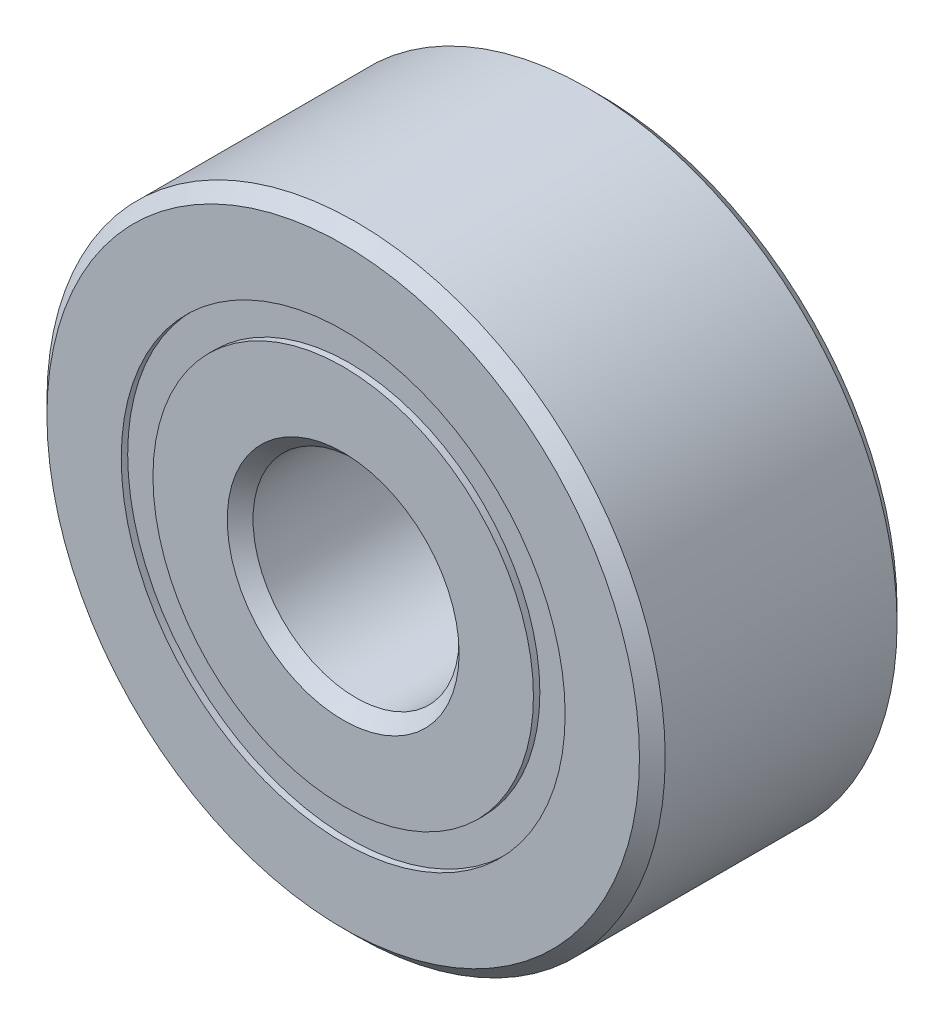
SolidWorks part; units mm, degrees
ref_plane "Front Plane" through (0, 0, 0) normal (0, 0, 1) x (1, 0, 0)
ref_plane "Top Plane" through (0, 0, 0) normal (0, 1, 0) x (1, 0, 0)
ref_plane "Right Plane" through (0, 0, 0) normal (1, 0, 0) x (0, 0, -1)
sketch "Sketch1" plane through (0, 0, 0) normal (1, 0, 0) x (0, 0, -1)
  line L0 (-1.9844, 0) -> (1.9844, 0) construction
  line L1 (0, 4.7625) -> (0, -4.7625) construction
  line L2 (1.7859, 4.7625) -> (-1.7859, 4.7625)
  line L3 (-1.7859, 4.7625) -> (-1.9844, 4.5641)
  line L4 (-1.9844, 4.5641) -> (-1.9844, 3.4192)
  line L5 (-1.9844, 3.4192) -> (-0.8819, 3.4192)
  line L6 (1.9844, 3.4192) -> (0.8819, 3.4192)
  line L7 (1.9844, 4.5641) -> (1.9844, 3.4192)
  line L8 (1.7859, 4.7625) -> (1.9844, 4.5641)
  line L9 (0, 4.7625) -> (0, 3.175) construction
  line L10 (0, 3.175) -> (0, 1.5875) construction
  arc A0 (-0.8819, 3.4192) -> (0.8819, 3.4192) centre (0, 3.175) cw
  point P14 (0, 1.5875)
  dimension "Width" = 3.9688
  dimension "OD" = 9.525
  dimension "D1" = 45
  dimension "D2" = 0.1984
  dimension "Shaft Dia" = 3.175
  dimension "D3" = 1.7639
  dimension "D4" = 0.2442
revolve "Revolve1" add sketch "Sketch1" angle 360 about L0
sketch "Sketch3" plane through (0, 0, 0) normal (1, 0, 0) x (0, 0, -1)
  line L0 (-1.9844, 2.9308) -> (-0.8819, 2.9308)
  line L1 (0, 4.7625) -> (0, -4.7625) construction
  line L2 (-1.9844, 4.5641) -> (-1.9844, 3.4192) construction
  line L3 (-1.9844, 2.9308) -> (-1.9844, 1.7859)
  line L4 (-1.7859, 4.7625) -> (-1.9844, 4.5641) construction
  line L5 (-1.9844, 1.7859) -> (-1.7859, 1.5875)
  line L6 (-1.7859, 1.5875) -> (1.7859, 1.5875)
  line L7 (1.7859, 4.7625) -> (1.7859, -4.7625) construction
  line L8 (1.7859, 1.5875) -> (1.9844, 1.7859)
  line L9 (1.9844, -4.5641) -> (1.9844, 4.5641) construction
  line L10 (1.9844, 1.7859) -> (1.9844, 2.9308)
  line L11 (1.9844, 2.9308) -> (0.8819, 2.9308)
  line L13 (1.7859, 4.7625) -> (1.9844, 4.5641) construction
  arc A0 (0.8819, 3.4192) -> (-0.8819, 3.4192) centre (0, 3.175) ccw construction
  arc A1 (0.8819, 2.9308) -> (-0.8819, 2.9308) centre (0, 3.175) cw
revolve "Revolve3" add sketch "Sketch3" angle 360 about L0
sketch "Sketch4" plane through (0, 0, 0) normal (1, 0, 0) x (0, 0, -1)
  line L0 (-0.9151, 3.175) -> (0.9151, 3.175)
  arc A2 (-0.9151, 3.175) -> (0.9151, 3.175) centre (0, 3.175) cw
  arc A3 (0.8819, 3.4192) -> (-0.8819, 3.4192) centre (0, 3.175) ccw construction
revolve "Revolve4" add sketch "Sketch4" angle 360 about L0
ref_axis "Axis1" through (0, 0, -1.9844) along (0, 0, 1)
pattern_circular "CirPattern1" count 6 every 60 about axis through (0, 0, -1.9844) along (0, 0, 1) of bodies 104
sketch "Sketch5" plane through (0, 0, 0) normal (1, 0, 0) x (0, 0, -1)
  line L0 (-1.9844, 3.4192) -> (-0.8819, 3.4192) construction
  line L1 (-1.8852, 3.4192) -> (-0.9151, 3.4192)
  line L2 (-1.8852, 3.4192) -> (-1.8852, 2.9308)
  line L3 (-1.8852, 2.9308) -> (-0.9151, 2.9308)
  line L4 (-0.9151, 3.4192) -> (-0.9151, 2.9308)
  line L5 (-1.9844, 2.9308) -> (-0.8819, 2.9308) construction
  line L6 (1.9844, 3.4192) -> (0.8819, 3.4192) construction
  line L7 (1.8852, 3.4192) -> (0.9151, 3.4192)
  line L8 (1.8852, 3.4192) -> (1.8852, 2.9308)
  line L9 (1.8852, 2.9308) -> (0.9151, 2.9308)
  line L10 (0.9151, 3.4192) -> (0.9151, 2.9308)
  line L11 (1.9844, 2.9308) -> (0.8819, 2.9308) construction
  line L12 (-1.7859, 4.7625) -> (-1.9844, 4.5641) construction
  point P18 (-1.8852, 4.6633)
revolve "Revolve5" add sketch "Sketch5" angle 360 about L0
equation "\"D2@Sketch1\" = \"Width@Sketch1\"*.05"
equation "\"D3@Sketch1\" = \"Width@Sketch1\"/2.25"
equation "\"D4@Sketch1\" = (((\"OD@Sketch1\"-\"Width@Sketch1\")/2)/3.25)/3.5"
equation "\"D2@CirPattern1\" = 360/\"Balls@CirPattern1\""
